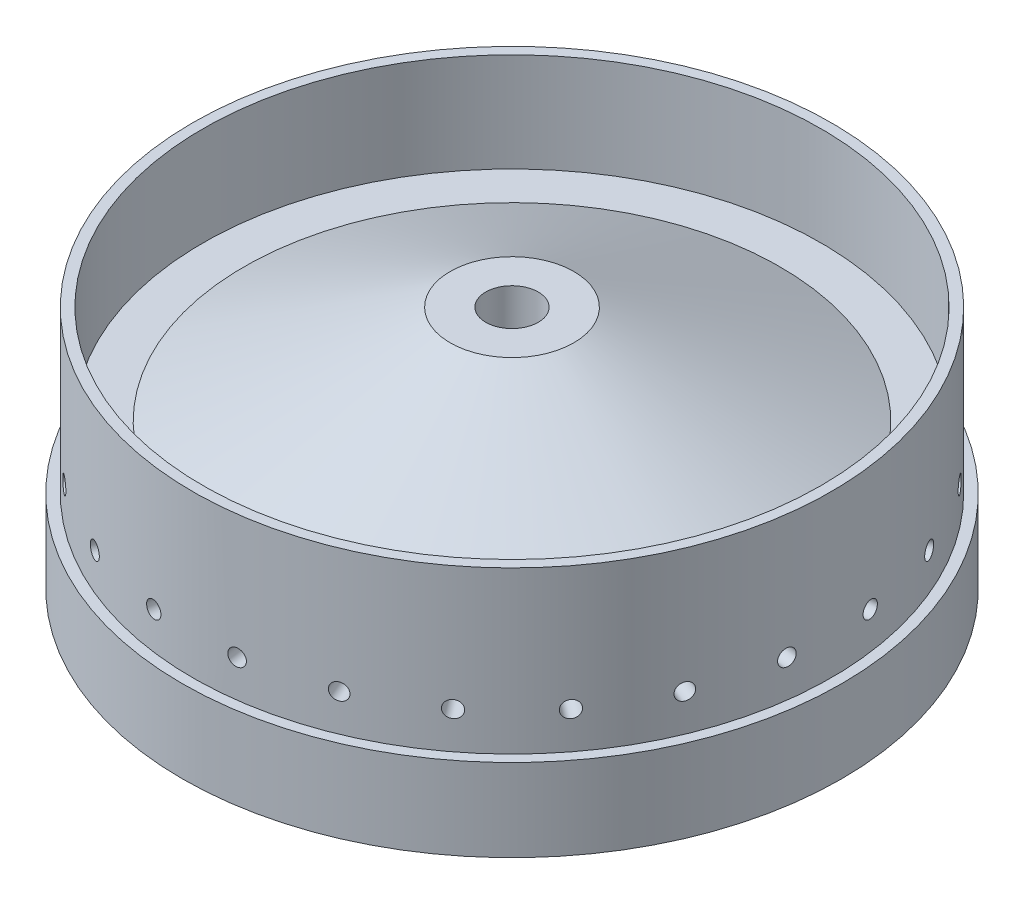
SolidWorks part; units mm, degrees
material "6061-T6 (SS)"
ref_plane "Front Plane" through (0, 0, 0) normal (0, 0, 1) x (1, 0, 0)
ref_plane "Top Plane" through (0, 0, 0) normal (0, 1, 0) x (1, 0, 0)
ref_plane "Right Plane" through (0, 0, 0) normal (1, 0, 0) x (0, 0, -1)
ref_plane "Plane1" through (0, 0, -75.0887) normal (0, 0, 1) x (1, 0, 0)
sketch "Sketch1" plane through (0, 0, 0) normal (0, 1, 0) x (1, 0, 0)
  line L1 (95.25, 0) -> (101.6, 0)
  line L2 (0, 0) -> (0, 61.9125) construction
  line L4 (101.6, 59.4931) -> (101.6, 0)
  line L6 (101.6, 59.4931) -> (8.0962, 59.4931) construction
  line L8 (0, 75.0887) -> (101.6, 75.0887)
  line L9 (101.6, 75.0887) -> (101.6, 59.4931)
  line L10 (8.0962, 0) -> (8.0962, 75.0887)
  line L11 (8.0962, 75.0887) -> (-8.0962, 75.0887)
  line L12 (-8.0962, 75.0887) -> (-8.0962, 0)
  line L13 (-8.0962, 0) -> (8.0962, 0)
  line L14 (8.0962, 59.4931) -> (0, 59.4931) construction
  line L15 (19.05, 75.0887) -> (82.55, 44.6088)
  line L16 (82.55, 44.6088) -> (95.25, 44.6088)
  line L17 (95.25, 44.6088) -> (95.25, 75.0887)
  ellipse E0 centre (0, 0) end of major axis (-95.25, 0) minor radius 59.4931
  point P18 (19.05, 75.0887)
  dimension "D4" = 15.5956
  dimension "D6" = 16.1925
  dimension "D7" = 6.35
  dimension "D8" = 30.48
  dimension "D9" = 12.7
  dimension "D10" = 19.05
  dimension "D2" = 101.6
  dimension "D3" = 75.0887
revolve "Revolve1" add sketch "Sketch1" angle 360 about L2 region at (66.7796, 0, -46.8658)
sketch "Sketch3" plane through (0, 0, 0) normal (0, 0, -1) x (-1, 0, 0)
  circle A0 centre (0, 0) radius 101.6
  circle A1 centre (0, 0) radius 98.425
  dimension "D1" = 203.2
  dimension "D2" = 3.175
extrude "Cut-Extrude2" cut sketch "Sketch3" along normal through all from offset 25.4
hole_wizard "1/4-20 Tapped Hole1" positions "3DSketch1" profile "Sketch10" tap size "1/4-20" standard "ANSI Inch"
sketch3d "3DSketch1"
  line L0 (97.583, 12.847, -36.83) -> (97.583, 12.847, 0) construction
  line L1 (97.583, 12.847, 0) -> (0, 0, 0) construction
  line L2 (0, 0, 0) -> (101.6, 0, 0) construction
  circle A0 centre (0, 0, 0) radius 101.6 construction
  point P0 (97.583, 12.847, -36.83)
  point P12 (0, 0, 101.6)
  dimension "D1" = 36.83
  dimension "D2" = 7.5
sketch "Sketch10" plane through (97.583, 12.847, -36.83) normal (0, 0, 1) x (-0.1305, 0.9914, 0)
  line L0 (0, 0) -> (0, 14.2338)
  line L1 (0, 14.2338) -> (2.5527, 12.7)
  line L2 (2.5527, 12.7) -> (2.5527, 0)
  line L5 (2.5527, 0) -> (0, 0)
  line L10 (0, 14.2338) -> (-2.5527, 12.7) construction
  line L11 (0, -6.35) -> (0, 107.95) construction
  dimension "Tap Drill Dia." = 5.1054
  dimension "Tap Drill Depth" = 12.7
  dimension "Drill Angle" = 118
cosmetic thread "Hole Thread2" parameters "D1"=12.7, "D2"=6.35
pattern_circular "CirPattern1" count 24 over 360 about axis through (0, 0, 0) along (0, 0, 1) of "1/4-20 Tapped Hole1"
sketch "Sketch13" plane through (0, 0, 0) normal (0, 0, 1) x (1, 0, 0)
  line L0 (-67.9108, -66.7883) -> (66.7883, 67.9108)
  line L1 (-66.7883, -67.9108) -> (67.9108, 66.7883)
  line L2 (0, 0) -> (0, -28.3739) construction
  circle A4 centre (0, 0) radius 95.25 construction
  arc A5 (-67.9108, -66.7883) -> (-66.7883, -67.9108) centre (0, 0) ccw
  arc A6 (66.7883, 67.9108) -> (67.9108, 66.7883) centre (0, 0) cw
  dimension "D1" = 1.5875
  dimension "D2" = 135
sketch "Sketch14" plane through (0, 0, -75.0888) normal (0, 0, -1) x (-1, 0, 0)
  circle A0 centre (0, 0) radius 8.0962
  circle A1 centre (0, 0) radius 8.0962 construction
move or copy body "Body-Move/Copy1" bodies to move or copy 120 copy no rotation origin (0, 0, -37.5444) rotation axis (1, 0, 0) rotation angle 90
equation "\"D7@Sketch1\"= .25"
equation "\"D1@Plane1\"= \"D3@Sketch1\""
